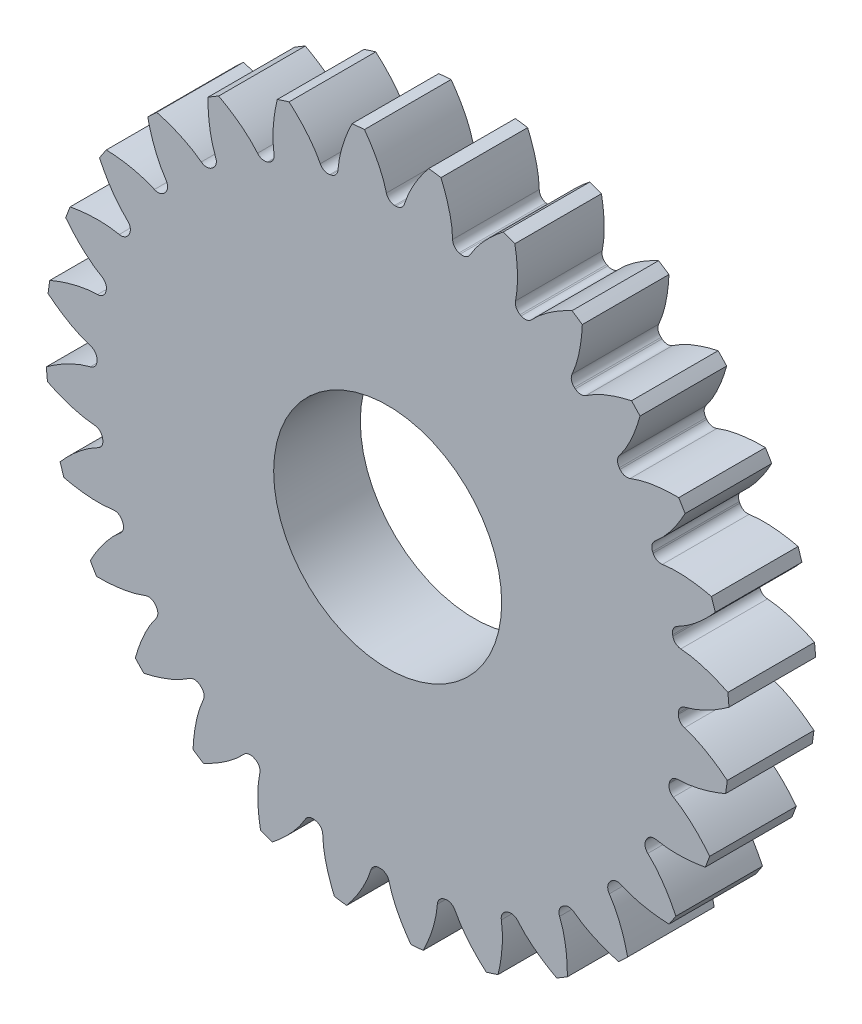
SolidWorks part; units mm, degrees
ref_plane "Front Plane" through (0, 0, 0) normal (0, 0, 1) x (1, 0, 0)
ref_plane "Top Plane" through (0, 0, 0) normal (0, 1, 0) x (1, 0, 0)
ref_plane "Right Plane" through (0, 0, 0) normal (1, 0, 0) x (0, 0, -1)
sketch "Sketch2" plane through (0, 0, 0) normal (0, 0, 1) x (1, 0, 0)
  spline S0 degree 4 poles (6.3442, 0) (6.347, 0) (6.3552, 0.0003) (6.3705, 0.0015) (6.3954, 0.0041) (6.4416, 0.0109) (6.4967, 0.0219) (6.5585, 0.0372) (6.6244, 0.0566) (6.6804, 0.0749) (6.7359, 0.0948) (6.7908, 0.116) (6.8568, 0.1435) (6.9353, 0.1789) (7.026, 0.2237) (7.1275, 0.2785) (7.2294, 0.3386) (7.3283, 0.4012) (7.4266, 0.4684) (7.5205, 0.5362) (7.6162, 0.6105) (7.7036, 0.6811) (7.7993, 0.7644) (7.8759, 0.8329) (7.9744, 0.9277) (8.0319, 0.985) (8.0983, 1.0535) (8.1273, 1.0847) (8.1452, 1.1039) knots 0 0 0 0 0 0.005377 0.015084 0.028532 0.04661 0.092111 0.119476 0.146842 0.174209 0.201575 0.228941 0.256307 0.307035 0.361767 0.4165 0.471232 0.525964 0.580697 0.635429 0.690161 0.744894 0.799626 0.854358 0.909091 0.954545 1 1 1 1 1 construction
  spline S1 degree 4 poles (6.3442, 0) (6.347, 0) (6.3552, 0.0003) (6.3705, 0.0015) (6.3954, 0.0041) (6.4416, 0.0109) (6.4967, 0.0219) (6.5585, 0.0372) (6.6244, 0.0566) (6.6804, 0.0749) (6.7359, 0.0948) (6.7908, 0.116) (6.8568, 0.1435) (6.9353, 0.1789) (7.026, 0.2237) (7.1275, 0.2785) (7.2294, 0.3386) (7.3283, 0.4012) (7.4266, 0.4684) (7.5205, 0.5362) (7.6162, 0.6105) (7.7036, 0.6811) (7.7993, 0.7644) (7.8759, 0.8329) (7.9531, 0.9071) (7.9904, 0.9438) (8.0093, 0.9627) knots 0 0 0 0 0 0.005377 0.015084 0.028532 0.04661 0.092111 0.119476 0.146842 0.174209 0.201575 0.228941 0.256307 0.307035 0.361767 0.4165 0.471232 0.525964 0.580697 0.635429 0.690161 0.744894 0.799626 0.854358 0.909091 0.909091 0.909091 0.909091 0.909091
sketch "Sketch3" plane through (0, 0, 0) normal (0, 0, 1) x (1, 0, 0)
  line L0 (0.3296, 0) -> (50000.3296, 0) construction
  line L2 (0, 0) -> (49814.8865, 4298.4979) construction
  circle A0 centre (0, 0) radius 6.5778 construction
  circle A1 centre (0, 0) radius 7.5
  circle A2 centre (0, 0) radius 6.375
  circle A3 centre (0, 0) radius 7 construction
  arc A4 (6.5187, 0.0277) -> (6.3732, -0.1525) centre (6.5631, -0.157) ccw
  arc A5 (6.4271, 1.0894) -> (6.2529, 1.242) centre (6.4392, 1.279) cw
  spline S0 degree 4 poles (-30.2224, 2999.4564) (5.0089, 26.9555) (5.4654, 0.3306) (5.9463, -0.0439) (6.3954, 0.0041) (6.4416, 0.0109) (6.4967, 0.0219) (6.5585, 0.0372) (6.6244, 0.0566) (6.6804, 0.0749) (6.7359, 0.0948) (6.7908, 0.116) (6.8568, 0.1435) (6.9353, 0.1789) (7.026, 0.2237) (7.1275, 0.2785) (7.2294, 0.3386) (7.3283, 0.4012) (7.4266, 0.4684) (7.5205, 0.5362) (7.6162, 0.6105) (7.7036, 0.6811) (7.7993, 0.7644) (8.3193, 1.2294) (10.3216, 3.414) (-32.0519, -38.6513) (2128.7274, 2122.6006) knots -0.792641 -0.792641 -0.792641 -0.792641 -0.792641 0.005377 0.015084 0.028532 0.04661 0.092111 0.119476 0.146842 0.174209 0.201575 0.228941 0.256307 0.307035 0.361767 0.4165 0.471232 0.525964 0.580697 0.635429 0.690161 0.744894 0.799626 0.854358 2.176469 2.176469 2.176469 2.176469 2.176469 only from (6.3442, 0) to (8.0093, 0.9627) construction
  spline S1 degree 4 poles (6.4271, 1.0894) (6.4471, 1.0881) (6.4817, 1.0852) (6.5309, 1.0798) (6.5945, 1.0706) (6.6526, 1.0605) (6.7103, 1.049) (6.7801, 1.0332) (6.8635, 1.0118) (6.9605, 0.9832) (7.0699, 0.9466) (7.1806, 0.9048) (7.2887, 0.8601) (7.3726, 0.8218) (7.4279, 0.7955) (7.4568, 0.7813) (7.4593, 0.78) knots 0.08222 0.08222 0.08222 0.08222 0.08222 0.119476 0.146842 0.174209 0.201575 0.228941 0.256307 0.307035 0.361767 0.4165 0.471232 0.525964 0.580697 0.586018 0.586018 0.586018 0.586018 0.586018
  spline S2 degree 4 poles (6.5187, 0.0277) (6.5382, 0.0324) (6.5718, 0.0411) (6.6194, 0.0549) (6.6804, 0.0749) (6.7359, 0.0948) (6.7908, 0.116) (6.8568, 0.1435) (6.9353, 0.1789) (7.026, 0.2237) (7.1275, 0.2785) (7.2294, 0.3386) (7.3283, 0.4012) (7.4044, 0.4533) (7.4544, 0.4887) (7.4804, 0.5076) (7.4827, 0.5093) knots 0.08222 0.08222 0.08222 0.08222 0.08222 0.119476 0.146842 0.174209 0.201575 0.228941 0.256307 0.307035 0.361767 0.4165 0.471232 0.525964 0.580697 0.586018 0.586018 0.586018 0.586018 0.586018
  point P11 (6.9741, 0.6018)
  point P16 (6.9969, 0.2098)
  dimension "D1" = 14
  dimension "D2" = 13.1557
  dimension "D3" = 15
  dimension "D4" = 12.75
  dimension "D5" = 0.19
  dimension "D6" = 0.3927
extrude "Boss-Extrude1" add sketch "Sketch3" along normal blind 1.9 contours A2 region at (0, 0, 0)
extrude "Boss-Extrude2" add sketch "Sketch3<3>" along normal up to surface (1.9 mm away) contours A4 S2 A1 S1 A5 A2 region at (6.8025, 0.587, 0) up to face at (6.375, 0, 1.9)
sketch "Sketch3<3>" plane through (0, 0, 0) normal (0, 0, 1) x (1, 0, 0) same geometry as "Sketch3"
pattern_circular "CirPattern1" count 28 over 360 about axis through (0, 0, 1.9) along (0, 0, -1) of "Boss-Extrude2"
sketch "Sketch4" plane through (0, 0, 1.9) normal (0, 0, 1) x (1, 0, 0)
  circle A0 centre (0, 0) radius 2.5
  dimension "D1" = 5
extrude "Cut-Extrude1" cut sketch "Sketch4" against normal through all
sketch "Sketch5" plane through (0, 0, 1.9) normal (0, 0, 1) x (1, 0, 0)
  circle A0 centre (0, 0) radius 7 construction
  circle A1 centre (0, 0) radius 7 construction
equation "\"m\"= 22.5 / 45mm'module"
equation "\"N\"= 28'number of teeth"
equation "\"a\"= 20deg'pressure angle"
equation "\"da\"= \"m\" * ( \"N\" + 2 )'addendum circle diameter"
equation "\"df\"= \"m\" * ( \"N\" - 2.5 )'dedendum circle diameter"
equation "\"db\"= \"m\" * \"N\" * cos ( \"a\" )'basic circle diameter"
equation "\"rb\"= \"db\" / 2'basic circle radius"
equation "\"s\"= \"m\" * pi / 2'pitch circle tooth thickness"
equation "\"r\"= \"m\" * 0.38'dedendum circle angle"
equation "\"B\"= \"d\" * 0.3'tooth width"
equation "\"d\"= 14mm"
equation "\"D1@Sketch3\"=\"d\""
equation "\"D2@Sketch3\"=\"db\""
equation "\"D3@Sketch3\"=\"da\""
equation "\"D4@Sketch3\"=\"df\""
equation "\"D5@Sketch3\"=\"r\""
equation "\"D6@Sketch3\"=\"s\"/2"
